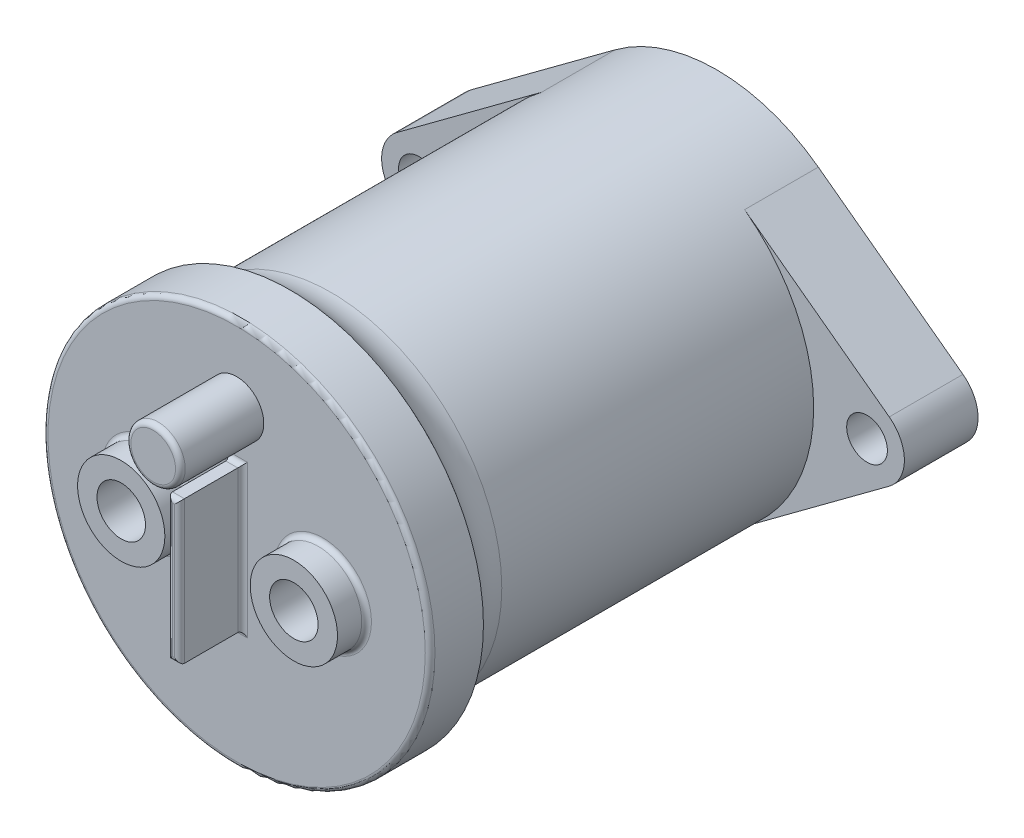
SolidWorks part; units mm, degrees
material "Custom Plastic"
ref_plane "X-Y Datum" through (0, 0, 0) normal (0, 0, 1) x (1, 0, 0)
ref_plane "X-Z Datum" through (0, 0, 0) normal (0, 1, 0) x (1, 0, 0)
ref_plane "Y-Z Datum" through (0, 0, 0) normal (1, 0, 0) x (0, 0, -1)
sketch "Sketch2" plane through (0, 0, 0) normal (0, 0, 1) x (1, 0, 0)
  circle A0 centre (0, 0) radius 17.6
  dimension "D1" = 35.2
extrude "Boss-Extrude1" add sketch "Sketch2" along normal blind 52.5
sketch "Sketch3" plane through (0, 0, 0) normal (0, 0, 1) x (1, 0, 0)
  line L0 (-23.1, 0) -> (23.1, 0) construction
  line L1 (-26.95, 0) -> (26.95, 0) construction
  line L2 (-25.3917, 3.0937) -> (-10.4762, 14.1425)
  line L3 (-25.3917, -3.0937) -> (-10.4762, -14.1425)
  line L4 (0, 28.5555) -> (0, -28.5555) construction
  line L5 (25.3917, -3.0937) -> (10.4762, -14.1425)
  line L6 (25.3917, 3.0937) -> (10.4762, 14.1425)
  circle A0 centre (23.1, 0) radius 2.1
  circle A1 centre (-23.1, 0) radius 2.1
  circle A2 centre (23.1, 0) radius 3.85
  circle A3 centre (-23.1, 0) radius 3.85
  circle A6 centre (0, 0) radius 17.6 construction
  circle A8 centre (0, 0) radius 17.6
  circle A9 centre (0, 0) radius 17.6
  point P4 (0, 0)
  point P10 (0, 0)
  point P23 (0, 0)
  dimension "D2" = 4.2
  dimension "D1" = 46.2
  dimension "D3" = 53.9
  dimension "D4" = 0
extrude "Boss-Extrude2" add sketch "Sketch3" along normal blind 7.6 contours A9 A2 L6 | A9 L5 A2 | A9 A2 A0 | A9 A3 A1 | A9 A3 L3 | A9 L2 A3 region at (-18.5342, 0, 0) region at (-21.417, 3.3412, 0) region at (18.5342, 0, 0) region at (26.4412, 1.683, 0)
sketch "Sketch4" plane through (0, 0, 52.5) normal (0, 0, 1) x (1, 0, 0)
  line L0 (-8.9, 0) -> (8.9, 0) construction
  line L1 (-0.615, 7.35) -> (0.615, 7.35)
  line L2 (-0.615, 7.35) -> (-0.615, -7.35)
  line L3 (-0.615, -7.35) -> (0.615, -7.35)
  line L4 (0.615, 7.35) -> (0.615, -7.35)
  line L5 (-0.615, 7.35) -> (0.615, -7.35) construction
  line L6 (-0.615, -7.35) -> (0.615, 7.35) construction
  circle A0 centre (-8.9, 0) radius 2.5
  circle A1 centre (8.9, 0) radius 2.5
  circle A2 centre (-8.9, 0) radius 4.5
  circle A3 centre (8.9, 0) radius 4.5
  point P0 (0, 0)
  point P11 (0, 0)
  dimension "D4" = 5
  dimension "D5" = 9
  dimension "D1" = 1.23
  dimension "D2" = 14.7
  dimension "D3" = 17.8
extrude "Boss-Extrude3" add sketch "Sketch4" along normal blind 3.5 contours L2 L1 L4 L3
sketch "Sketch5" plane through (0, 0, 52.5) normal (0, 0, 1) x (1, 0, 0)
  line L4 (0.615, 7.35) -> (-0.615, 7.35)
  line L5 (0.615, -7.35) -> (0.615, 7.35)
  line L6 (-0.615, -7.35) -> (0.615, -7.35)
  line L7 (-0.615, 7.35) -> (-0.615, -7.35)
  line L8 (0.615, 7.35) -> (-0.615, 7.35)
  line L9 (0.615, -7.35) -> (0.615, 7.35)
  line L10 (-0.615, -7.35) -> (0.615, -7.35)
  line L11 (-0.615, 7.35) -> (-0.615, -7.35)
  circle A1 centre (8.9, 0) radius 4.5
  circle A2 centre (8.9, 0) radius 4.5
  circle A3 centre (-8.9, 0) radius 4.5
  circle A4 centre (-8.9, 0) radius 4.5
  circle A5 centre (8.9, 0) radius 2.5
  circle A6 centre (8.9, 0) radius 2.5
  circle A7 centre (-8.9, 0) radius 2.5
  circle A8 centre (-8.9, 0) radius 2.5
  circle M22 centre (0, 0) radius 17.6
  line M23 (0.615, 7.35) -> (0.615, -7.35)
  line M24 (0.615, -7.35) -> (-0.615, -7.35)
  line M25 (-0.615, -7.35) -> (-0.615, 7.35)
  line M26 (-0.615, 7.35) -> (0.615, 7.35)
  dimension "D1" = 0
  dimension "D2" = 0
  dimension "D3" = 0
  dimension "D4" = 0
  dimension "D5" = 0
extrude "Cut-Extrude1" cut sketch "Sketch5" against normal blind 3 contours A4 A2 M22 M26 M23 M24 M25 | A8 | A6 region at (8.9, 0, 52.5) region at (-8.9, 0, 52.5) region at (-17.1022, 0, 52.5)
sketch "Sketch7" plane through (0, 0, 49.5) normal (0, 0, 1) x (1, 0, 0)
  circle A0 centre (0, 0) radius 19.95
  dimension "D1" = 39.9
extrude "Boss-Extrude5" add sketch "Sketch7" against normal blind 5.5
fillet "Fillet3" radius 5 1 edges at (17.6, 0, 44)
fillet "Fillet4" radius 0.5 11 edges at (-0.615, 0, 56) (0, 7.35, 56) (0.615, 0, 56) (0, -7.35, 56) (19.95, 0, 49.5) (-0.615, 0, 49.5) (0, -7.35, 49.5) (0.615, 0, 49.5) (0, 7.35, 49.5) (13.4, 0, 49.5) (-4.4, 0, 49.5)
sketch "Sketch8" plane through (0, 0, 52.5) normal (0, 0, 1) x (1, 0, 0)
  circle A0 centre (-8.9, 0) radius 2.5 construction
  circle A1 centre (8.9, 0) radius 2.5
  circle A2 centre (8.9, 0) radius 2.5
  circle A3 centre (-8.9, 0) radius 2.5
  dimension "D1" = 0
extrude "Cut-Extrude2" cut sketch "Sketch8" against normal blind 7
sketch "Sketch10" plane through (0, 0, 49.5) normal (0, 0, 1) x (1, 0, 0)
  line L0 (0, 0) -> (0, 12.15) construction
  line L1 (0.615, 7.35) -> (-0.615, 7.35) construction
  circle A0 centre (0, 12.15) radius 2.8
  point P2 (0, 9.35)
  dimension "D1" = 5.6
  dimension "D2" = 2
extrude "Boss-Extrude6" add sketch "Sketch10" along normal blind 8.6
fillet "Fillet5" radius 0.5 1 edges at (2.8, 12.15, 58.1)
ref_plane "Plane3" through (0, 0, 0) normal (0.1736, 0.9848, 0) x (0, 0, -1)
ref_plane "Plane4" through (0, 0, 0) normal (0.9848, -0.1736, 0) x (0, 0, -1)
